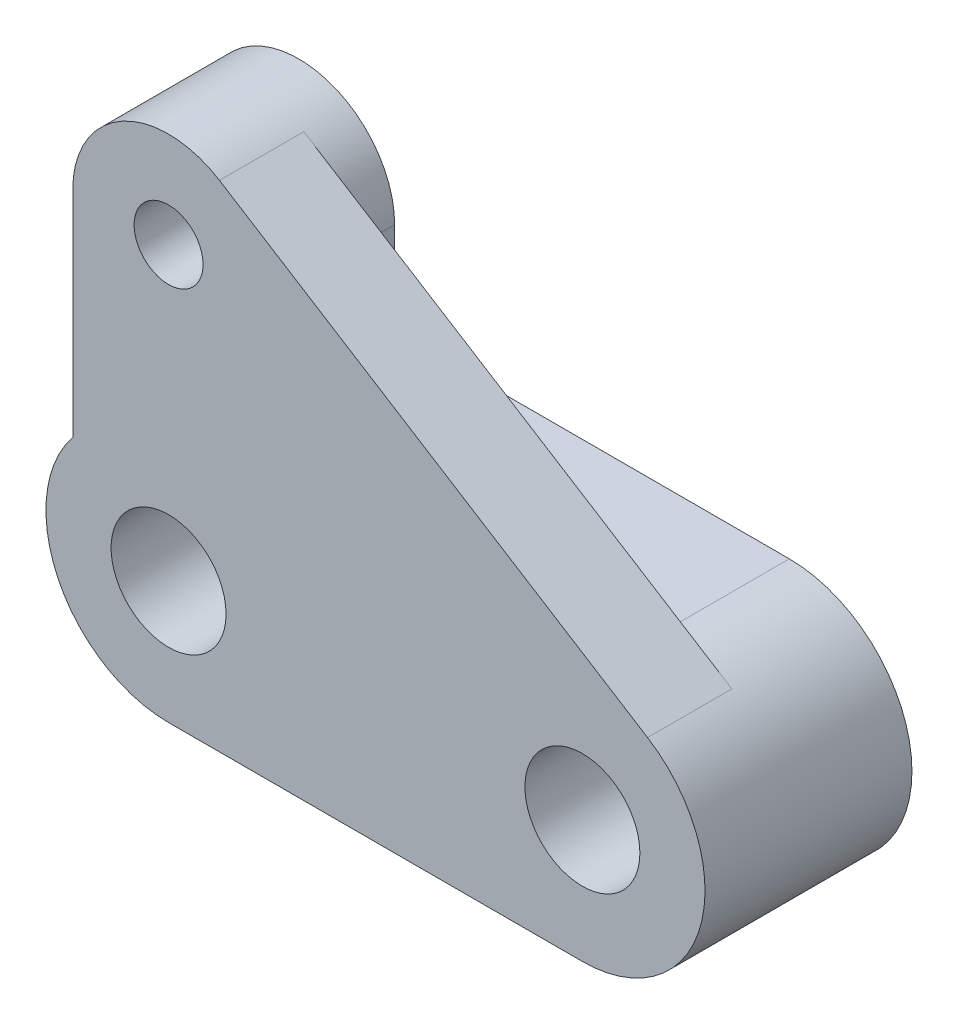
SolidWorks part; units mm, degrees
material "Titanium Ti-13V-11Cr-3Al Solution Treated"
ref_plane "Front Plane" through (0, 0, 0) normal (0, 0, 1) x (1, 0, 0)
ref_plane "Top Plane" through (0, 0, 0) normal (0, 1, 0) x (1, 0, 0)
ref_plane "Right Plane" through (0, 0, 0) normal (1, 0, 0) x (0, 0, -1)
sketch "Sketch1" plane through (0, 0, 0) normal (0, 0, 1) x (1, 0, 0)
  line L0 (-108, 32) -> (0, 32)
  line L1 (0, -32) -> (-108, -32)
  circle A0 centre (0, 0) radius 15
  arc A1 (0, -32) -> (0, 32) centre (0, 0) ccw
  arc A2 (-108, 32) -> (-108, -32) centre (-108, 0) ccw
  circle A3 centre (-108, 0) radius 15
  dimension "D1" = 30
  dimension "D2" = 64
  dimension "D3" = 108
extrude "Boss-Extrude1" add sketch "Sketch1" along normal mid plane 54
sketch "Sketch2" plane through (0, 0, 27) normal (0, 0, 1) x (1, 0, 0)
  line L0 (0, 32) -> (-108, 32) construction
  line L1 (0, 32) -> (-25, 32)
  line L2 (25, 76) -> (25, 19.975)
  line L3 (-25, 76) -> (-25, 32)
  line L4 (-54, 32) -> (-54, -32) construction
  line L5 (-108, -32) -> (0, -32) construction
  line L6 (-83, 76) -> (-83, 32)
  line L7 (-108, 32) -> (-83, 32)
  line L8 (-133, 76) -> (-133, 19.975)
  arc A0 (25, 76) -> (-25, 76) centre (0, 76) ccw
  circle A1 centre (0, 76) radius 9
  arc A2 (0, -32) -> (0, 32) centre (0, 0) ccw construction
  arc A3 (25, 19.975) -> (0, 32) centre (0, 0) ccw
  circle A4 centre (-108, 76) radius 9
  arc A5 (-133, 76) -> (-83, 76) centre (-108, 76) cw
  arc A6 (-133, 19.975) -> (-108, 32) centre (-108, 0) cw
  point P23 (0, 0)
  dimension "D1" = 18
  dimension "D2" = 50
  dimension "D3" = 76
extrude "Boss-Extrude3" add sketch "Sketch2" against normal blind 34 contours L8 A6 L7 L6 A5
extrude "Cut-Extrude1" cut sketch "Sketch2<3>" against normal blind 34 contours A4
sketch "Sketch2<3>" plane through (0, 0, 27) normal (0, 0, 1) x (1, 0, 0) same geometry as "Sketch2"
fillet "Fillet1" radius 15 1 edges at (-83, 32, 10)
sketch "Sketch3" plane through (0, 0, 27) normal (0, 0, 1) x (1, 0, 0)
  line L0 (-94.7166, 97.179) -> (17.0027, 27.1092)
  line L4 (0, 32) -> (-68, 32)
  line L5 (-83, 47) -> (-83, 76)
  line L6 (-133, 76) -> (-133, 19.975)
  line L7 (-108, -32) -> (0, -32)
  line L8 (0, 32) -> (-68, 32)
  line L9 (-83, 47) -> (-83, 76)
  arc A4 (-83, 47) -> (-68, 32) centre (-68, 47) ccw
  arc A5 (-83, 76) -> (-133, 76) centre (-108, 76) ccw
  arc A6 (-133, 19.975) -> (-108, -32) centre (-108, 0) ccw
  arc A7 (0, -32) -> (0, 32) centre (0, 0) ccw
  arc A8 (-83, 47) -> (-68, 32) centre (-68, 47) ccw
  arc A9 (-83, 76) -> (-94.7166, 97.179) centre (-108, 76) ccw
  arc A11 (17.0027, 27.1092) -> (0, 32) centre (0, 0) ccw
  dimension "D1" = 0
extrude "Boss-Extrude4" add sketch "Sketch3" against normal blind 22
